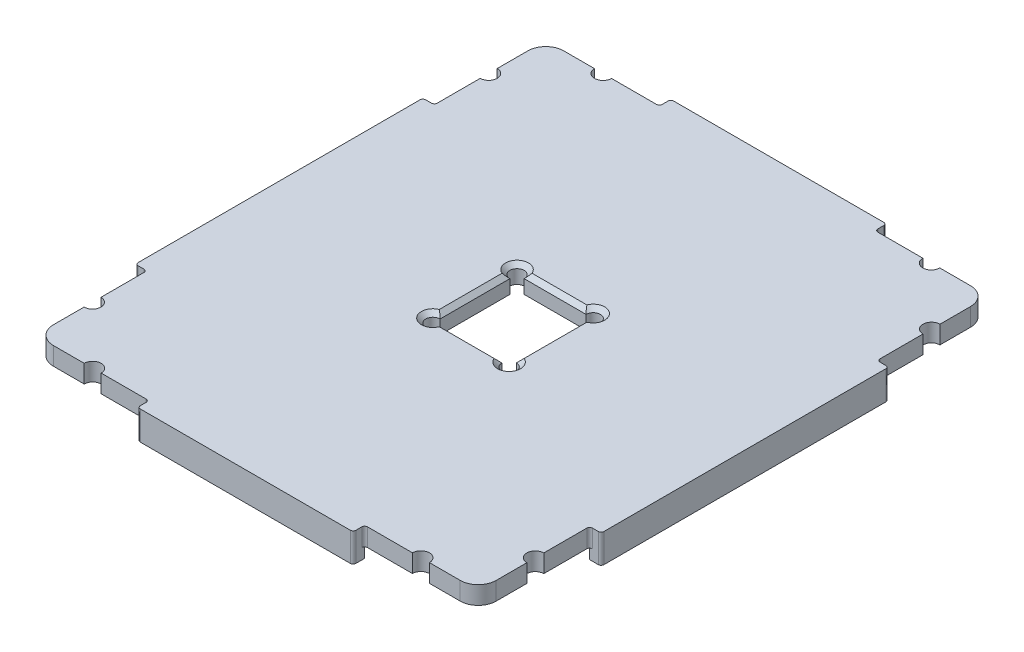
SolidWorks part; units mm, degrees
ref_plane "Front Plane" through (0, 0, 0) normal (0, 0, 1) x (1, 0, 0)
ref_plane "Top Plane" through (0, 0, 0) normal (0, 1, 0) x (1, 0, 0)
ref_plane "Right Plane" through (0, 0, 0) normal (1, 0, 0) x (0, 0, -1)
sketch "Sketch1" plane through (0, 0, 0) normal (0, 1, 0) x (1, 0, 0)
  line L1 (-39.116, 45.085) -> (39.116, 45.085)
  line L2 (-39.116, 45.085) -> (-39.116, -45.085)
  line L3 (-39.116, -45.085) -> (39.116, -45.085)
  line L4 (39.116, 45.085) -> (39.116, -45.085)
  line L5 (-5.334, 7.493) -> (5.588, 7.493)
  line L6 (-6.604, 6.223) -> (-6.604, -6.096)
  line L7 (-5.334, -7.366) -> (5.588, -7.366)
  line L8 (6.858, 6.223) -> (6.858, -6.096)
  arc A0 (-5.334, 7.493) -> (-6.604, 6.223) centre (-6.604, 7.493) ccw
  arc A1 (6.858, 6.223) -> (5.588, 7.493) centre (6.858, 7.493) ccw
  arc A2 (5.588, -7.366) -> (6.858, -6.096) centre (6.858, -7.366) ccw
  arc A3 (-6.604, -6.096) -> (-5.334, -7.366) centre (-6.604, -7.366) ccw
  dimension "D9" = 2.54
  dimension "D10" = 2.54
  dimension "D11" = 2.54
  dimension "D12" = 2.54
  dimension "D1" = 78.232
  dimension "D2" = 90.17
  dimension "D3" = 39.116
  dimension "D4" = 45.085
  dimension "D5" = 13.462
  dimension "D6" = 6.858
  dimension "D7" = 14.859
  dimension "D8" = 7.366
extrude "Boss-Extrude1" add sketch "Sketch1" along normal blind 3.175
fillet "Fillet1" radius 3.175 4 edges at (-39.116, 1.5875, -45.085) (39.116, 1.5875, -45.085) (39.116, 1.5875, 45.085) (-39.116, 1.5875, 45.085)
sketch "Sketch2" plane through (0, 3.175, 0) normal (0, 1, 0) x (1, 0, 0)
  line L0 (19.05, -47.117) -> (19.05, -45.085)
  line L1 (-39.116, 41.91) -> (-39.116, -41.91) construction
  line L2 (-41.148, 25.4) -> (-39.116, 25.4)
  line L3 (-41.148, 25.4) -> (-41.148, -25.4)
  line L4 (-41.148, -25.4) -> (-39.116, -25.4)
  line L5 (-39.116, 25.4) -> (-39.116, -25.4)
  line L6 (0, 45.085) -> (0, -45.085) construction
  line L7 (35.941, 45.085) -> (-35.941, 45.085) construction
  line L8 (-35.941, -45.085) -> (35.941, -45.085) construction
  line L9 (-39.116, 0) -> (39, 0) construction
  line L10 (-19.05, 47.117) -> (19.05, 47.117)
  line L11 (-19.05, 47.117) -> (-19.05, 45.085)
  line L12 (39.116, 25.4) -> (39.116, -25.4)
  line L13 (41.148, -25.4) -> (39.116, -25.4)
  line L14 (41.148, 25.4) -> (41.148, -25.4)
  line L15 (41.148, 25.4) -> (39.116, 25.4)
  line L16 (-19.05, 45.085) -> (19.05, 45.085)
  line L17 (19.05, 47.117) -> (19.05, 45.085)
  line L18 (-19.05, -45.085) -> (19.05, -45.085)
  line L19 (-19.05, -47.117) -> (-19.05, -45.085)
  line L20 (-19.05, -47.117) -> (19.05, -47.117)
  point P4 (-39.116, 0)
  dimension "D1" = 50.8
  dimension "D2" = 2.032
  dimension "D3" = 25.4
  dimension "D9" = 19.05
  dimension "D10" = 38.1
  dimension "D12" = 2.032
extrude "Boss-Extrude2" add sketch "Sketch2" against normal blind 5.08
fillet "Fillet3" radius 0.508 16 edges at (-39.116, 1.5875, 25.4) (-41.148, 0.635, 25.4) (-41.148, 0.635, -25.4) (-39.116, 1.5875, -25.4) (-19.05, 0.635, -47.117) (-19.05, 1.5875, -45.085) (19.05, 0.635, -47.117) (19.05, 1.5875, -45.085) (39.116, 1.5875, -25.4) (41.148, 0.635, -25.4) (41.148, 0.635, 25.4) (39.116, 1.5875, 25.4) (19.05, 0.635, 47.117) (19.05, 1.5875, 45.085) (-19.05, 0.635, 47.117) (-19.05, 1.5875, 45.085)
sketch "Sketch3" plane through (0, 3.175, 0) normal (0, 1, 0) x (1, 0, 0)
  line L0 (-39.116, 41.91) -> (-39.116, 25.908) construction
  line L1 (-19.558, 45.085) -> (-35.941, 45.085) construction
  line L2 (-41.148, 24.892) -> (-41.148, -24.892) construction
  line L3 (18.542, 47.117) -> (-18.542, 47.117) construction
  line L4 (-41.148, 0) -> (41.148, 0) construction
  line L5 (41.148, -24.892) -> (41.148, 24.892) construction
  line L6 (0, 47.117) -> (0, -47.032) construction
  line L9 (-39.116, 36.5) -> (-39.116, 33.5)
  line L10 (-27.5, 45.085) -> (-30.5, 45.085)
  line L11 (27.5, 45.085) -> (30.5, 45.085)
  line L12 (39.116, 36.5) -> (39.116, 33.5)
  line L13 (39.116, -33.5) -> (39.116, -36.5)
  line L14 (30.5, -45.085) -> (27.5, -45.085)
  line L15 (-27.5, -45.085) -> (-30.5, -45.085)
  line L16 (-39.116, -36.5) -> (-39.116, -33.5)
  arc A0 (-39.116, 33.5) -> (-39.116, 36.5) centre (-39.116, 35) ccw
  arc A1 (-30.5, 45.085) -> (-27.5, 45.085) centre (-29, 45.085) ccw
  arc A2 (30.5, 45.085) -> (27.5, 45.085) centre (29, 45.085) cw
  arc A3 (39.116, 33.5) -> (39.116, 36.5) centre (39.116, 35) cw
  arc A4 (39.116, -33.5) -> (39.116, -36.5) centre (39.116, -35) ccw
  arc A5 (30.5, -45.085) -> (27.5, -45.085) centre (29, -45.085) ccw
  arc A6 (-30.5, -45.085) -> (-27.5, -45.085) centre (-29, -45.085) cw
  arc A7 (-39.116, -33.5) -> (-39.116, -36.5) centre (-39.116, -35) cw
  point P8 (-41.148, 0)
  point P11 (0, 47.117)
  dimension "D1" = 3
  dimension "D3" = 3
  dimension "D2" = 35
  dimension "D4" = 29
extrude "Cut-Extrude1" cut sketch "Sketch3" against normal through all
chamfer "Chamfer2" distance 0.762 angle 45 8 edges at (-7.502, 3.175, 8.264) (0.127, 3.175, 7.366) (7.756, 3.175, 8.264) (6.858, 3.175, -0.0635) (7.756, 3.175, -8.391) (-6.604, 3.175, -0.0635) (-7.502, 3.175, -8.391) (0.127, 3.175, -7.493)
